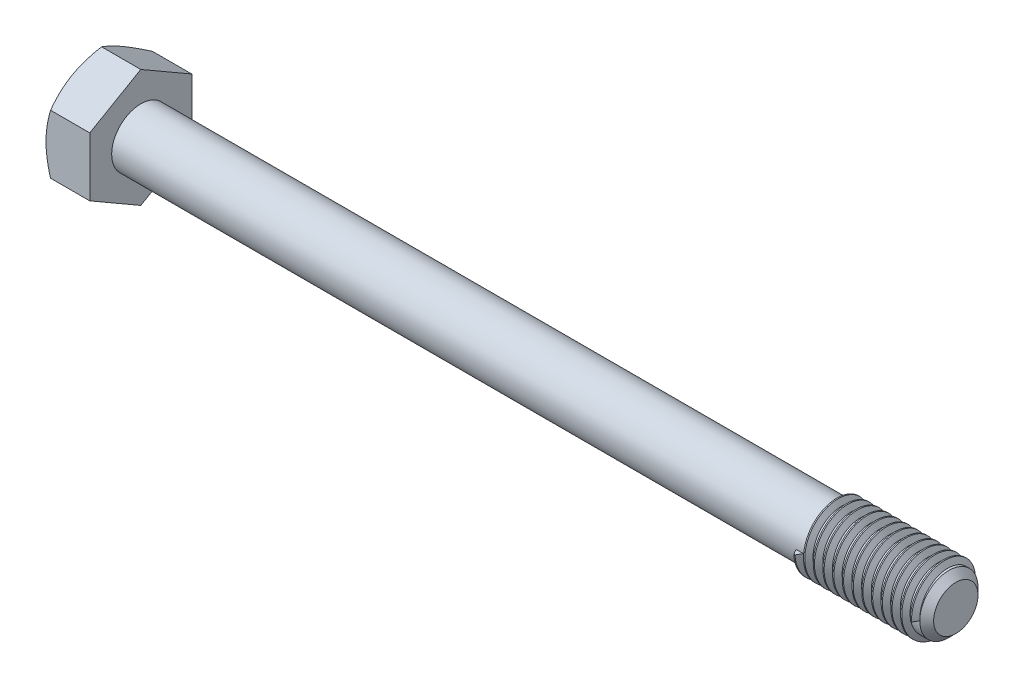
SolidWorks part; units mm, degrees
extrude "BaseHead" add sketch "Sketch1" along normal blind 4.7752
sketch "Sketch1" plane through (0, 0, 0) normal (1, 0, 0) x (0, 0, -1)
  line L0 (5.5626, 3.2116) -> (5.5626, -3.2116)
  line L1 (-5.5626, 3.2116) -> (-5.5626, -3.2116)
  line L2 (5.5626, -3.2116) -> (0, -6.4231)
  line L3 (0, -6.4231) -> (-5.5626, -3.2116)
  line L4 (5.5626, 3.2116) -> (0, 6.4231)
  line L5 (0, 6.4231) -> (-5.5626, 3.2116)
  dimension "D2" = 120
  dimension "D3" = 5.5626
  dimension "D4" = 5.5626
  dimension "D5" = 5.5626
ref_plane "Plane1" through (0, 0, 0) normal (0, 0, 1) x (1, 0, 0)
ref_plane "Plane2" through (0, 0, 0) normal (0, 1, 0) x (1, 0, 0)
ref_plane "Plane3" through (0, 0, 0) normal (1, 0, 0) x (0, 0, -1)
sketch "BodySke" plane through (0, 0, 0) normal (0, 0, 1) x (1, 0, 0)
  line L0 (0, 3.2116) -> (0, -3.2116) construction
  line L1 (0, 0) -> (93.6752, 0)
  line L2 (0, 0) -> (0, 3.175)
  line L3 (0, 3.175) -> (92.9195, 3.175)
  line L4 (93.6752, 0) -> (93.6752, 2.4193)
  line L5 (4.7752, 6.4231) -> (4.7752, 3.2116) construction
  line L6 (93.6752, 2.4193) -> (92.9195, 3.175)
  line L7 (0, 0) -> (96.52, 0) construction
  line L8 (93.6752, -2.4193) -> (92.9195, -3.175) construction
  line L9 (0, -3.175) -> (92.9195, -3.175) construction
  line L10 (6.0452, 15.24) -> (6.0452, -2.54) construction
  line L11 (74.6252, 15.24) -> (74.6252, -2.54) construction
  line L12 (4.7752, 3.2116) -> (4.7752, -3.2116) construction
  dimension "Diameter" = 6.35
  dimension "Advance" = 1.27
revolve "BaseBody" add sketch "BodySke" angle 360 about L7
cosmetic thread "ThreadCosmetic" [suppressed] parameters "Thread_length"=19.05, "Thread_minor"=4.8387
sketch "Sketch3" plane through (0, 0, 0) normal (0, 0, 1) x (1, 0, 0)
  line L0 (0, 5.5626) -> (4.163, 12.7731)
  line L1 (0, 6.4231) -> (0, 3.2116) construction
  line L2 (4.163, 12.7731) -> (4.163, 19.1231)
  line L3 (4.163, 19.1231) -> (-12.7, 19.1231)
  line L4 (-12.7, 19.1231) -> (-12.7, 5.5626)
  line L5 (-12.7, 5.5626) -> (0, 5.5626)
  line L6 (0, 0) -> (99.06, 0) construction
  line L7 (4.7752, 6.4231) -> (0, 6.4231) construction
  dimension "D1" = 5.5626
  dimension "D2" = 6.35
  dimension "D3" = 12.7
  dimension "D4" = 6.35
  dimension "Head_ch_ang" = 30
revolve "HeadChamfer" cut sketch "Sketch3" angle 360 about L6
fillet "HeadFillet" [suppressed] radius 0.762
sketch "ThdSchSke" plane through (0, 0, 0) normal (0, 0, 1) x (1, 0, 0)
  line L0 (74.6252, -2.4193) -> (74.0961, -3.175)
  line L1 (74.6252, -2.4193) -> (75.1543, -3.175)
  line L2 (75.1543, -3.175) -> (75.1543, -3.9687)
  line L3 (-3.175, 0) -> (5.1513, 0) construction
  line L5 (75.1543, -3.9687) -> (74.0961, -3.9687)
  line L6 (74.0961, -3.9687) -> (74.0961, -3.175)
  dimension "Thread_minor" = 4.8387
  dimension "Diameter" = 6.35
  dimension "Start" = 74.6252
revolve "ThreadSchematic" [suppressed] cut sketch "ThdSchSke" angle 360 about L3
pattern_linear "ThdSchPat" [suppressed]
thread "Thread1" pitch 1.0583 method extrude profile "Thread Profile1" start angle 0, offset 0, length 12.7, pitch 1.0583, diameter 6.35
ref_plane "Plane4" through (92.9195, 0, 3.175) normal (0, -1, 0) x (0, 0, 1)
sketch "Thread Profile1" plane through (92.9195, 0, 3.175) normal (0, -1, 0) x (0, 0, 1)
  line L0 (0, 0) -> (0, 1.0583) construction
  line L1 (0, 0) -> (0.5728, 0.3307)
  line L2 (0.5728, 0.3307) -> (0.5728, 0.463)
  line L3 (0.5728, 0.463) -> (0, 0.7937)
  line L4 (0.5728, 0.3969) -> (0, 0.3969) construction
  line L11 (0, 0) -> (0, 0.7937)
  point P2 (0, 0)
  dimension "Pitch" = 1.0583
  dimension "Profile_Angle" = 60
  dimension "Profile_Land" = 0.1323
  dimension "Profile_Height" = 0.5728
equation "\"D3@Sketch1\" = \"Width_flats@Sketch1\" / 2"
equation "\"D4@Sketch1\" = \"D3@Sketch1\""
equation "\"D5@Sketch1\" = \"D4@Sketch1\""
equation "\"Thread_minor@ThreadCosmetic\" = \"Minor_dia@BodySke\""
equation "\"D1@Sketch3\" = \"Width_flats@Sketch1\" / 2"
equation "\"Thread_length@ThreadCosmetic\" = ((sgn( (\"Length@BodySke\" - \"Advance@BodySke\" ) - \"Thread_nom@BodySke\" )-1)*( (\"Length@BodySke\" - \"Advance@BodySke\" ) - \"Thread_nom@BodySke\" ))/-2+ \"Thread_nom@BodySke\""
equation "\"Thread_minor@ThdSchSke\" = \"Minor_dia@BodySke\""
equation "\"Diameter@ThdSchSke\" = \"Diameter@BodySke\""
equation "\"Overcut@ThdSchSke\" = \"Diameter@BodySke\" * 1.25"
equation "\"Start@ThdSchSke\" = \"Head_ht@BaseHead\" + \"Length@BodySke\" - \"Thread_length@ThreadCosmetic\"  '---Non-countersunk---"
equation "\"Num_threads@ThdSchPat\" = int( \"Thread_length@ThreadCosmetic\" / \"Advance@BodySke\" + 0.999 )  + 1"
equation "\"Advance@ThdSchPat\" = \"Thread_length@ThreadCosmetic\" /  (\"Num_threads@ThdSchPat\" - 1) 'relax it"
equation "\"Num_threads@ThdSchPat\" = \"Num_threads@ThdSchPat\" - sgn( \"Num_threads@ThdSchPat\" - 1) '---chamfered tips only---"
